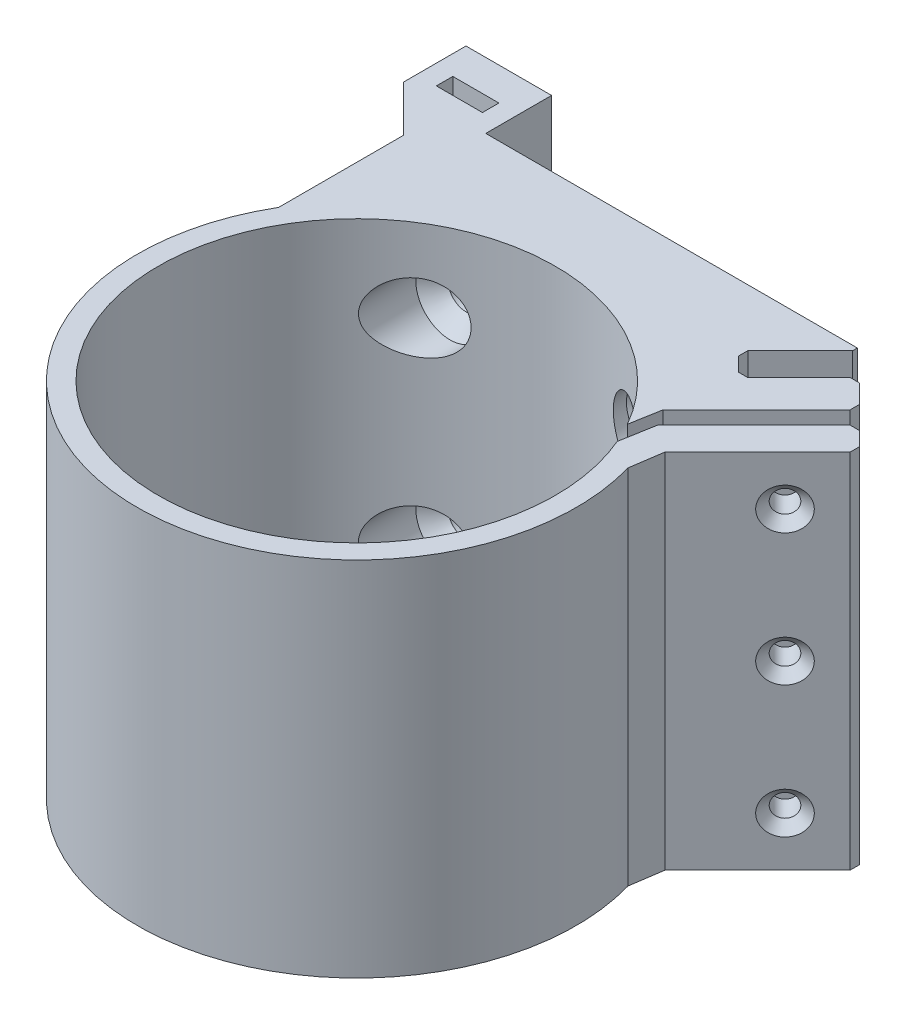
SolidWorks part; units mm, degrees
ref_plane "Front Plane" through (0, 0, 0) normal (0, 0, 1) x (1, 0, 0)
ref_plane "Top Plane" through (0, 0, 0) normal (0, 1, 0) x (1, 0, 0)
ref_plane "Right Plane" through (0, 0, 0) normal (1, 0, 0) x (0, 0, -1)
sketch "Sketch1" plane through (0, 0, 0) normal (0, 1, 0) x (1, 0, 0)
  line L0 (-28.75, 16.8768) -> (-28.75, 35.8375)
  line L5 (-35.75, 52.3375) -> (-22.75, 52.3375)
  line L6 (-22.75, 52.3375) -> (-22.75, 36.3375)
  line L7 (-22.75, 36.3375) -> (22.75, 36.3375)
  line L8 (22.75, 36.3375) -> (22.75, 42.3375)
  line L9 (22.75, 42.3375) -> (35.75, 42.3375)
  line L11 (27.0756, 19.4499) -> (26.2619, 14.8353)
  line L12 (28.6751, 17.0037) -> (27.7579, 11.8016)
  line L14 (27.0756, 19.4499) -> (41.9926, 34.3669)
  line L15 (28.6751, 17.0037) -> (44.0155, 32.3441)
  line L16 (44.0155, 32.3441) -> (47.5511, 28.8085)
  line L17 (47.5511, 28.8085) -> (31.0017, 12.2591)
  line L19 (37.75, 38.6096) -> (28.5576, 29.4172)
  line L20 (28.5576, 29.4172) -> (25.0221, 32.9527)
  line L21 (25.0221, 32.9527) -> (35.75, 43.6806)
  line L24 (37.75, 38.6096) -> (41.9926, 34.3669)
  line L25 (35.75, 43.6806) -> (35.75, 42.3375)
  line L26 (-35.75, 52.3375) -> (-35.75, 42.8375)
  line L27 (-35.75, 42.8375) -> (-28.75, 35.8375)
  line L35 (-32.75, 44.8375) -> (-25.75, 44.8375)
  line L36 (-32.75, 44.8375) -> (-32.75, 47.3375)
  line L37 (-32.75, 47.3375) -> (-25.75, 47.3375)
  line L38 (-25.75, 44.8375) -> (-25.75, 47.3375)
  line L39 (-32.75, 44.8375) -> (-25.75, 47.3375) construction
  line L40 (-32.75, 47.3375) -> (-25.75, 44.8375) construction
  arc A0 (-28.75, 16.8768) -> (31.0017, 12.2591) centre (0, 0) ccw
  arc A1 (26.2619, 14.8353) -> (27.7579, 11.8016) centre (0, 0) ccw
  arc A3 (31.0017, 12.2591) -> (-28.75, 16.8768) centre (0, 0) ccw construction
  circle A4 centre (0, 0) radius 32.1625 construction
  point P5 (35.75, 43.6806)
  point P9 (0, 36.3375)
  point P12 (-29.25, 46.0875)
  point P13 (0, 33.3375)
  point P37 (-29.25, 52.3375)
  dimension "D2" = 3.175
  dimension "D4" = 30.1625
  dimension "D22" = 64.325
  dimension "D3" = 45.5
  dimension "D5" = 3
  dimension "D6" = 3
  dimension "D7" = 6
  dimension "D8" = 10
  dimension "D9" = 13
  dimension "D10" = 145
  dimension "D11" = 16
  dimension "D12" = 5
  dimension "D13" = 6
  dimension "D14" = 5
  dimension "D15" = 2
  dimension "D16" = 4
  dimension "D17" = 2
  dimension "D18" = 5
  dimension "D19" = 7
  dimension "D20" = 2.5
  dimension "D21" = 135
  dimension "D23" = 6
  dimension "D24" = 2
extrude "Boss-Extrude1" add sketch "Sketch1" along normal mid plane 55 contours A1 L11 L14 L19 L20 L21 L9 L8 L7 L6 L5 L0 A0 L17 L16 L15 L12 region at (-27.555, 0, -26.3572)
hole_wizard "CSK for M3 Flat Head Machine Screw1" positions "Sketch2" profile "Sketch3" countersink size "M3" standard "ANSI Metric"
sketch "Sketch2" plane through (9.3713, 0, 9.3713) normal (0.7071, 0, 0.7071) x (0.7071, 0, -0.7071)
  line L2 (53.9944, 27.5) -> (53.9944, -27.5) construction
  point P0 (45.9944, 20)
  point P2 (45.9944, 0)
  point P4 (45.9944, -20)
  dimension "D1" = 20
  dimension "D2" = 20
  dimension "D3" = 8
sketch "Sketch3" plane through (41.8942, 20, -23.1517) normal (0, 1, 0) x (0.7071, 0, -0.7071)
  line L0 (0, 0) -> (0, 21.0113)
  line L1 (0, 21.0113) -> (1.7, 19.9898)
  line L2 (1.7, 19.9898) -> (1.7, 1.45)
  line L3 (1.7, 1.45) -> (3.15, 0)
  line L5 (3.15, 0) -> (0, 0)
  line L6 (-1.7, 1.45) -> (-3.15, 0) construction
  line L10 (0, 21.0113) -> (-1.7, 19.9898) construction
  line L11 (0, -6.35) -> (0, 107.95) construction
  dimension "Hole Dia." = 3.4
  dimension "Hole Depth" = 19.9898
  dimension "Near C'Sink Dia." = 6.3
  dimension "Near C'Sink Angle" = 90
  dimension "Drill Angle" = 118
sketch "Sketch4" plane through (0, 27.5, 0) normal (0, -1, 0) x (1, 0, 0)
  line L1 (-22.75, -36.3375) -> (22.75, -36.3375)
  line L2 (-22.75, -36.3375) -> (-22.75, -42.3375)
  line L3 (-22.75, -42.3375) -> (22.75, -42.3375)
  line L4 (22.75, -36.3375) -> (22.75, -42.3375)
extrude "Boss-Extrude2" add sketch "Sketch4" along normal blind 4.5
ref_plane "Plane1" through (0, 0, -30.1625) normal (0, 0, 1) x (1, 0, 0)
sketch "Sketch6" plane through (0, 0, -30.1625) normal (0, 0, 1) x (1, 0, 0)
  line L1 (16, -15) -> (-16, -15) construction
  line L2 (16, -15) -> (16, 15) construction
  line L3 (16, 15) -> (-16, 15) construction
  line L4 (-16, -15) -> (-16, 15) construction
  line L5 (16, -15) -> (-16, 15) construction
  line L6 (16, 15) -> (-16, -15) construction
  point P0 (0, 0)
  dimension "D1" = 32
  dimension "D2" = 30
hole_wizard "CSK for M5 Flat Head Machine Screw1" positions "Sketch10" profile "Sketch12" countersink size "M5" standard "ANSI Metric" end condition through all
sketch "Sketch10" plane through (0, 0, -30.1625) normal (0, 0, 1) x (1, 0, 0)
  point P0 (-16, 15)
  point P3 (16, 15)
  point P6 (16, -15)
  point P9 (-16, -15)
sketch "Sketch12" plane through (-16, 15, -30.1625) normal (1, 0, 0) x (0, -1, 0)
  line L0 (0, 0) -> (0, 22.175)
  line L1 (0, 22.175) -> (2.75, 22.175)
  line L2 (2.75, 22.175) -> (2.75, 2.45)
  line L3 (2.75, 2.45) -> (5.2, 0)
  line L5 (5.2, 0) -> (0, 0)
  line L6 (-2.75, 2.45) -> (-5.2, 0) construction
  line L11 (0, -6.35) -> (0, 107.95) construction
  dimension "Thru Hole Dia." = 5.5
  dimension "Thru Hole Depth" = 22.175
  dimension "Near C'Sink Dia." = 10.4
  dimension "Near C'Sink Angle" = 90
sketch "Sketch13" plane through (0, 0, -30.1625) normal (0, 0, 1) x (1, 0, 0)
  circle A0 centre (-16, -15) radius 5.2 construction
  circle A1 centre (16, -15) radius 5.2 construction
  circle A2 centre (16, 15) radius 5.2 construction
  circle A3 centre (-16, 15) radius 5.2 construction
  circle A4 centre (-16, -15) radius 5.2
  circle A5 centre (16, -15) radius 5.2
  circle A6 centre (16, 15) radius 5.2
  circle A7 centre (-16, 15) radius 5.2
extrude "Cut-Extrude1" cut sketch "Sketch13" along normal up to next
chamfer "Chamfer1" distance 1 angle 45 7 edges at (47.5511, 0, -28.8085) (44.0155, 0, -32.3441) (28.5576, 0, -29.4172) (25.0221, 0, -32.9527) (41.9926, 0, -34.3669) (37.75, 0, -38.6096) (34.4069, 0, -42.3375) first distance on face at (44.1216, 20, -25.3791) first distance on face at (45.7833, 0, -30.5763) first distance on face at (33.2952, 20, -34.1548) first distance on face at (26.7898, 0, -31.185) first distance on face at (35.1337, 20, -27.508) first distance on face at (39.8713, 0, -36.4883) first distance on face at (27.3555, 20, -35.2862)
chamfer "Chamfer2" distance 3 angle 30 1 edges at (31.0017, 0, -12.2591) first distance on face at (-0.7214, 0, 9.3352)
sketch "Sketch14" plane through (0, 0, -52.3375) normal (0, 0, -1) x (-1, 0, 0)
  line L0 (32.75, 27.5) -> (32.75, -27.5) construction
  line L1 (25.75, 27.5) -> (25.75, -27.5) construction
  line L2 (32.75, 27.5) -> (32.75, -27.5)
  line L3 (25.75, 27.5) -> (25.75, -27.5)
  line L5 (32.75, -10) -> (25.75, -10)
  line L6 (32.75, -10) -> (32.75, 10)
  line L7 (32.75, 10) -> (25.75, 10)
  line L8 (25.75, -10) -> (25.75, 10)
  line L9 (32.75, -10) -> (25.75, 10) construction
  line L10 (32.75, 10) -> (25.75, -10) construction
  point P4 (29.25, 0)
  point P9 (31.75, 8.7211)
  point P10 (0, 0)
  dimension "D1" = 20
extrude "Cut-Extrude2" cut sketch "Sketch14" against normal up to surface (5 mm away) contours L2 L7 L3 L5 region at (-29.25, 0, -52.3375) up to face at (-29.25, 0, -47.3375)
hole_wizard "CSK for M3 SFHCS1" positions "Sketch17" profile "Sketch18" countersink size "M3" standard "ANSI Metric" end condition up to next
sketch "Sketch17" plane through (-35.75, 0, 0) normal (-1, 0, 0) x (0, 0, 1)
  line L0 (-52.3375, 27.5) -> (-52.3375, -27.5) construction
  line L1 (-47.3375, 10) -> (-52.3375, 10) construction
  line L2 (-47.3375, -10) -> (-52.3375, -10) construction
  point P0 (-48.3375, 5)
  point P2 (-48.3375, -5)
  point P7 (0, 0)
  dimension "D1" = 4
  dimension "D2" = 5
  dimension "D3" = 5
sketch "Sketch18" plane through (-35.75, 5, -48.3375) normal (0, 1, 0) x (0, 0, 1)
  line L0 (0, 0) -> (0, 3)
  line L1 (0, 3) -> (1.7, 3)
  line L2 (1.7, 3) -> (1.7, 1.66)
  line L3 (1.7, 1.66) -> (3.36, 0)
  line L5 (3.36, 0) -> (0, 0)
  line L6 (-1.7, 1.66) -> (-3.36, 0) construction
  line L11 (0, -6.35) -> (0, 107.95) construction
  dimension "Thru Hole Dia." = 3.4
  dimension "Thru Hole Depth" = 3
  dimension "Near C'Sink Dia." = 6.72
  dimension "Near C'Sink Angle" = 90
hole_wizard "Tap Drill for M3x0.5 Tap1" positions "Sketch19" profile "Sketch20" hole size "M3x0.5" standard "ANSI Metric" end condition up to next
sketch "Sketch19" plane through (-25.75, 0, 0) normal (-1, 0, 0) x (0, 0, 1)
  point P0 (-48.3375, 5)
  point P3 (-48.3375, -5)
sketch "Sketch20" plane through (-25.75, 5, -48.3375) normal (0, 1, 0) x (0, 0, 1)
  line L0 (0, 0) -> (0, 3)
  line L1 (0, 3) -> (1.25, 3)
  line L2 (1.25, 3) -> (1.25, 0)
  line L5 (1.25, 0) -> (0, 0)
  line L11 (0, -6.35) -> (0, 107.95) construction
  dimension "Thru Hole Dia." = 2.5
  dimension "Thru Hole Depth" = 3
